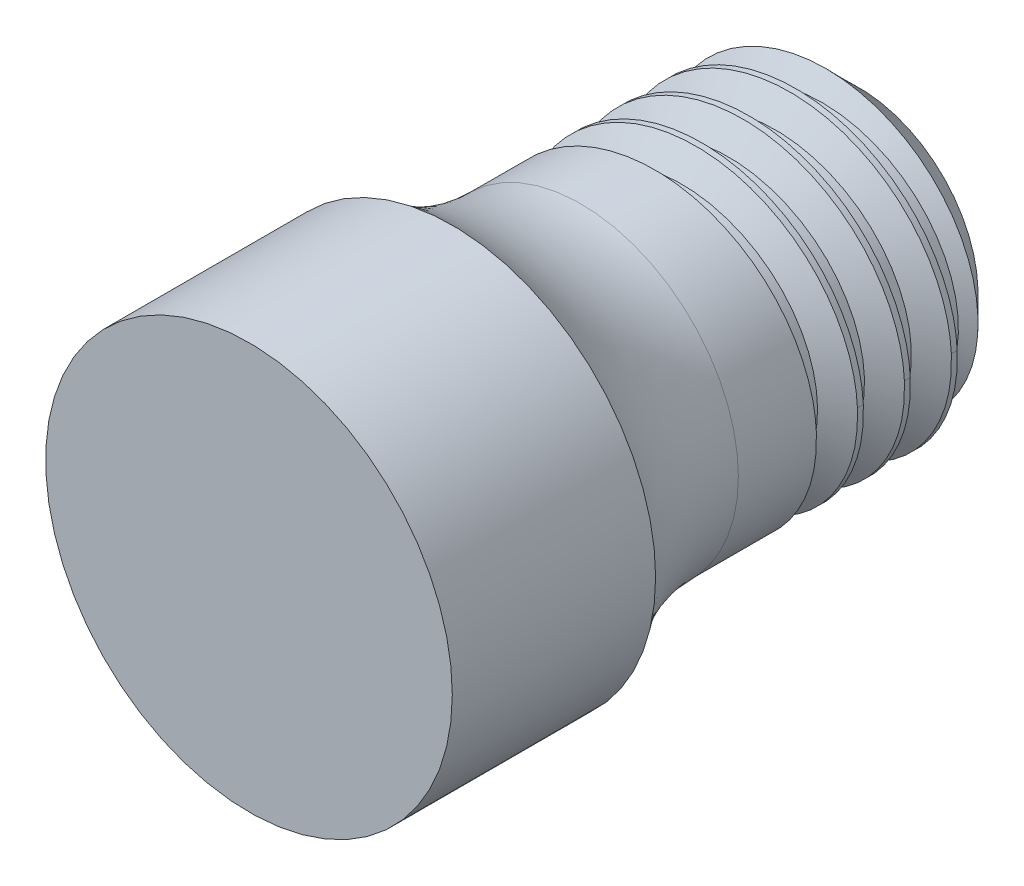
SolidWorks part; units mm, degrees
ref_plane "Front Plane" through (0, 0, 0) normal (0, 0, 1) x (1, 0, 0)
ref_plane "Top Plane" through (0, 0, 0) normal (0, 1, 0) x (1, 0, 0)
ref_plane "Right Plane" through (0, 0, 0) normal (1, 0, 0) x (0, 0, -1)
sketch "Sketch1" plane through (0, 0, 0) normal (0, 0, 1) x (1, 0, 0)
  circle A1 centre (0, 0) radius 10
  dimension "D1" = 20
extrude "Boss-Extrude1" add sketch "Sketch1" along normal blind 10
sketch "Sketch2" plane through (0, 0, 0) normal (0, 0, -1) x (-1, 0, 0)
  circle A0 centre (0, 0) radius 7.75
  dimension "D1" = 15.5
extrude "Boss-Extrude2" add sketch "Sketch2" along normal blind 20
thread "Thread1" pitch 2.3091 method cut profile "Thread Profile1" start angle 0, offset 9, length 10, pitch 2.3091, diameter 15.5
ref_plane "Plane1" through (-7.75, 0, -9) normal (0, -1, 0) x (-1, 0, 0)
sketch "Thread Profile1" plane through (-7.75, 0, -9) normal (0, -1, 0) x (-1, 0, 0)
  line L0 (0, 0) -> (0, 2.3091) construction
  line L11 (0, 0) -> (0, 2.0205)
  line L12 (0, 2.0205) -> (-1.2498, 1.2989)
  line L13 (-1.2498, 1.2989) -> (-1.2498, 0.7216)
  line L15 (-1.2498, 0.7216) -> (0, 0)
  line L17 (-1.2498, 1.0102) -> (0, 1.0102) construction
  point P2 (0, 0)
  dimension "Pitch" = 2.3091
  dimension "Profile_Angle" = 60
  dimension "Profile_Land" = 0.5773
  dimension "Profile_Height" = 1.2498
sketch "Sketch5" plane through (0, 0, 0) normal (1, 0, 0) x (0, 0, -1)
  line L0 (17.4, 8.4567) -> (20, 5.8567)
  line L1 (20, 5.8567) -> (20, 8.4567)
  line L2 (20, 8.4567) -> (17.4, 8.4567)
  line L3 (20, -7.75) -> (20, 6.7747) construction
  line L4 (-5, 0) -> (34.2291, 0) construction
  dimension "D1" = 2.6
revolve "Cut-Revolve1" cut sketch "Sketch5" angle 360 about L4
fillet "Fillet1" radius 10 1 edges at (-7.75, 0, 0)
